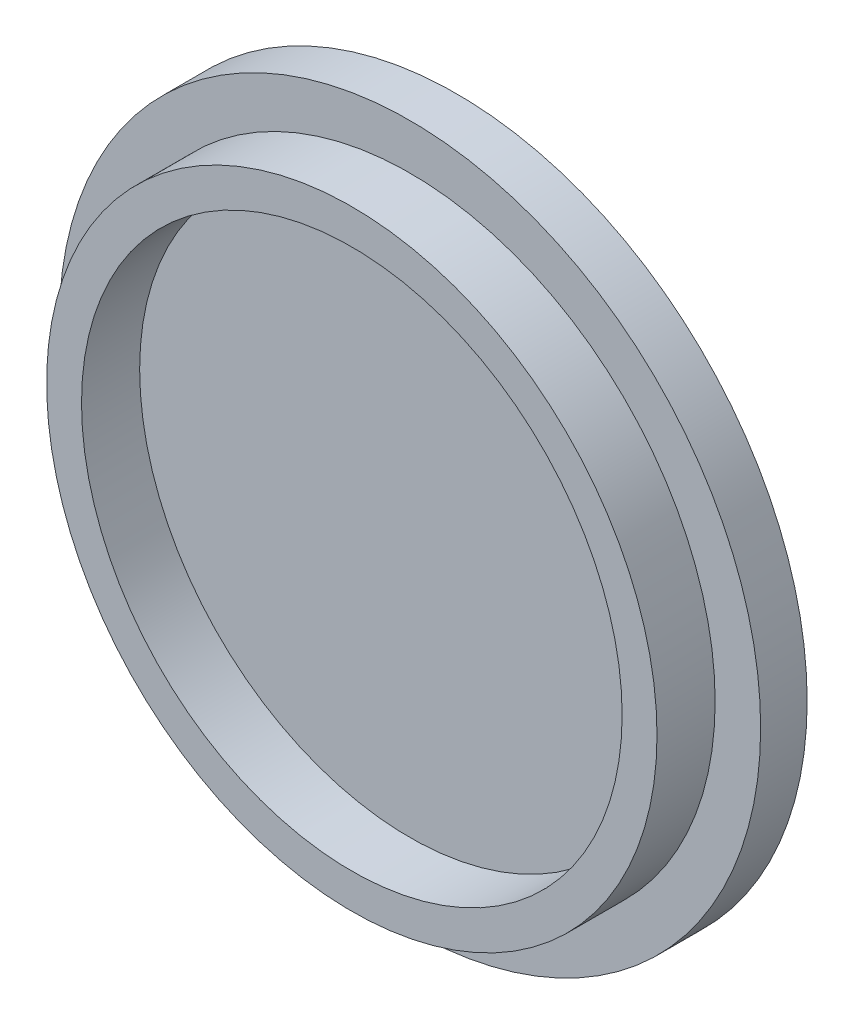
SolidWorks part; units mm, degrees
ref_plane "Alzado" through (0, 0, 0) normal (0, 0, 1) x (1, 0, 0)
ref_plane "Planta" through (0, 0, 0) normal (0, 1, 0) x (1, 0, 0)
ref_plane "Vista lateral" through (0, 0, 0) normal (1, 0, 0) x (0, 0, -1)
sketch "Croquis1" plane through (0, 0, 0) normal (0, 0, 1) x (1, 0, 0)
  circle A0 centre (0, 0) radius 30.165
  dimension "D1" = 60.33
extrude "Saliente-Extruir1" add sketch "Croquis1" along normal blind 2 and the other way blind 2
sketch "Croquis3" plane through (0, 0, 2) normal (0, 0, 1) x (1, 0, 0)
  circle A0 centre (0, 0) radius 26.25
  circle A1 centre (0, 0) radius 23.25
  dimension "D1" = 52.5
  dimension "D2" = 3
extrude "Saliente-Extruir2" add sketch "Croquis3" along normal blind 5
